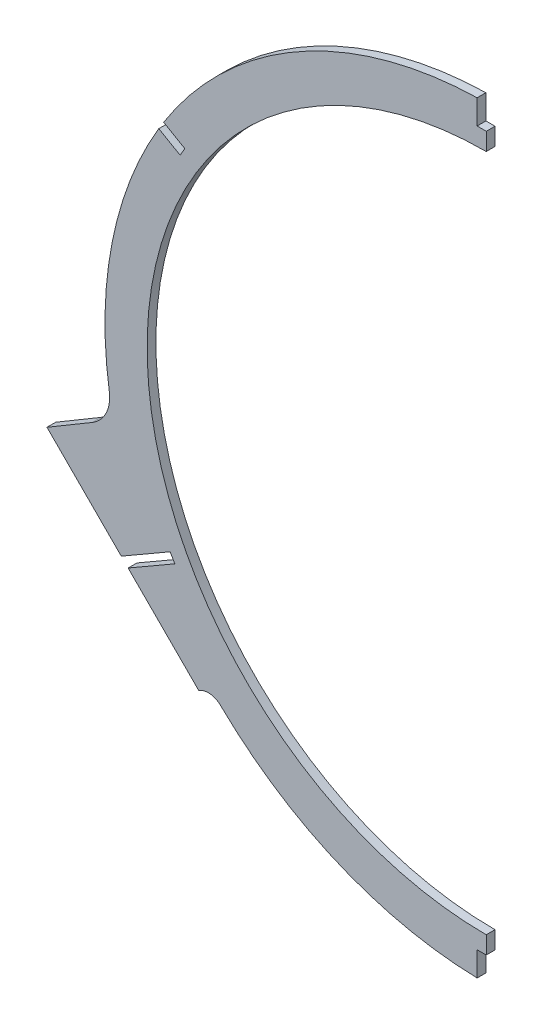
SolidWorks part; units mm, degrees
material "Plywood"
ref_plane "Front Plane" through (0, 0, 0) normal (0, 0, 1) x (1, 0, 0)
ref_plane "Top Plane" through (0, 0, 0) normal (0, 1, 0) x (1, 0, 0)
ref_plane "Right Plane" through (0, 0, 0) normal (1, 0, 0) x (0, 0, -1)
sketch "Sketch1" plane through (0, 0, 0) normal (0, 0, 1) x (1, 0, 0)
  line L0 (0, 0) -> (0, 499.9473) construction
  line L1 (0, -114.7984) -> (0, -129.4545) construction
  line L2 (0, -374.4718) -> (0, 404.2655) construction
  line L3 (-1.651, 142.9921) -> (-1.651, 150.6121) construction
  line L4 (1.651, 142.9921) -> (1.651, 150.6121) construction
  line L5 (-1.651, 142.9921) -> (1.651, 142.9921) construction
  line L6 (136.2041, -53.806) -> (0.0002, 24.7625) construction
  line L7 (-136.2076, -53.7991) -> (0.0002, 24.7625) construction
  line L8 (136.2041, -53.806) -> (0.0002, 24.7625) construction
  line L9 (-136.2076, -53.7991) -> (0.0002, 24.7625) construction
  line L10 (-125.0584, -45.4626) -> (-118.4576, -41.6554) construction
  line L11 (-123.6259, -48.4483) -> (-116.8078, -44.5157) construction
  line L12 (-118.4576, -41.6554) -> (-116.8078, -44.5157) construction
  line L13 (-124.1455, -48.7479) -> (-123.6847, -48.4822) construction
  line L14 (-123.6847, -48.4822) -> (-123.6259, -48.4483) construction
  line L15 (-125.7952, -45.8876) -> (-125.1113, -45.4931) construction
  line L16 (-125.1113, -45.4931) -> (-125.0584, -45.4626) construction
  line L17 (125.4797, -45.7137) -> (125.1075, -45.499) construction
  line L18 (123.8298, -48.5739) -> (123.6807, -48.488) construction
  line L19 (117.0223, -44.647) -> (118.6722, -41.7868) construction
  line L20 (123.6807, -48.488) -> (123.6228, -48.4545) construction
  line L21 (123.6228, -48.4545) -> (117.0223, -44.647) construction
  line L22 (125.1075, -45.499) -> (125.0554, -45.4689) construction
  line L23 (125.0554, -45.4689) -> (118.6722, -41.7868) construction
  line L24 (-107.079, -46.8884) -> (-120.3798, -54.5735)
  line L25 (-108.6638, -44.1348) -> (-121.9647, -51.8199)
  line L28 (-115.4206, -47.9666) -> (-121.9445, -51.7361) construction
  line L29 (-120.2754, -54.5131) -> (-108.646, -44.1245) construction
  line L30 (-114.4607, -49.3188) -> (-122.1124, -53.7399) construction
  line L31 (-113.7686, -50.8257) -> (-120.3665, -54.6379) construction
  line L32 (-115.4206, -47.9666) -> (-113.7686, -50.8257) construction
  line L33 (106.3137, -46.4532) -> (129.9098, -60.0883)
  line L34 (107.9004, -43.7007) -> (131.505, -57.3407)
  line L35 (129.9098, -60.0883) -> (131.505, -57.3407)
  line L36 (129.9098, -60.0883) -> (131.505, -57.3407) construction
  line L37 (107.9004, -43.7007) -> (131.505, -57.3407) construction
  line L38 (106.3137, -46.4532) -> (129.9098, -60.0883) construction
  line L39 (129.9098, -60.0883) -> (107.9004, -43.7007) construction
  line L40 (118.9051, -51.8945) -> (101.8722, -42.0519) construction
  line L41 (120.3631, -54.6438) -> (113.7655, -50.8313)
  line L42 (122.0152, -51.7848) -> (122.0057, -51.7794) construction
  line L43 (113.7655, -50.8313) -> (115.4176, -47.9723)
  line L44 (122.0057, -51.7794) -> (121.9413, -51.7421) construction
  line L45 (121.9413, -51.7421) -> (115.4176, -47.9723)
  line L46 (-108.6638, -44.1348) -> (-121.9647, -51.8199)
  line L47 (-107.079, -46.8884) -> (-120.3798, -54.5735)
  arc A0 (-1.651, 150.6121) -> (-125.0584, -45.4626) centre (0, 12.7) ccw
  circle A1 centre (0, 12.7) radius 120.904
  arc A2 (0, 150.622) -> (-1.651, 150.6121) centre (0, 12.7) ccw
  circle A3 centre (0, 12.7) radius 137.922 construction
  arc A4 (1.651, 150.6121) -> (0, 150.622) centre (0, 12.7) ccw
  arc A5 (-124.3508, -46.9604) -> (-123.6259, -48.4483) centre (0, 12.7) ccw
  arc A6 (-123.6259, -48.4483) -> (-121.9445, -51.7361) centre (0, 12.7) ccw
  arc A7 (-125.0584, -45.4626) -> (-124.3508, -46.9604) centre (0, 12.7) ccw
  arc A8 (124.3477, -46.9667) -> (125.0554, -45.4689) centre (0, 12.7) ccw
  arc A9 (125.0554, -45.4689) -> (1.651, 150.6121) centre (0, 12.7) ccw
  arc A10 (123.6228, -48.4545) -> (124.3477, -46.9667) centre (0, 12.7) ccw
  arc A11 (-121.9153, -51.7914) -> (-121.1641, -53.1919) centre (0, 12.7) ccw
  arc A12 (-120.3665, -54.6379) -> (120.3631, -54.6438) centre (0, 12.7) ccw
  arc A13 (-121.9445, -51.7361) -> (-121.9153, -51.7914) centre (0, 12.7) ccw
  arc A14 (-121.1641, -53.1919) -> (-120.3827, -54.6089) centre (0, 12.7) ccw
  arc A15 (-120.3827, -54.6089) -> (-120.397, -54.5834) centre (0, 12.7) ccw construction
  arc A16 (-120.397, -54.5834) -> (-120.3665, -54.6379) centre (0, 12.7) ccw construction
  arc A17 (120.3936, -54.5893) -> (121.0149, -53.4654) centre (0, 12.7) ccw construction
  arc A18 (121.9413, -51.7421) -> (123.6228, -48.4545) centre (0, 12.7) ccw
  arc A19 (120.3631, -54.6438) -> (120.3936, -54.5893) centre (0, 12.7) ccw construction
  arc A20 (121.0149, -53.4654) -> (121.9121, -51.7974) centre (0, 12.7) ccw construction
  arc A21 (121.9121, -51.7974) -> (121.9413, -51.7421) centre (0, 12.7) ccw construction
  spline S0 degree 3 poles (106.3137, -46.4532) (106.8426, -45.5357) (107.3715, -44.6182) (107.9004, -43.7007) knots 0 0 0 0 1 1 1 1 weights 1 1 1 1
  spline S1 degree 3 poles (-66.0123, 133.6164) (-70.0128, 131.4329) (-73.8716, 129.0699) (-81.3156, 123.9975) (-84.9009, 121.288) (-91.7995, 115.5249) (-95.113, 112.4712) (-99.0811, 108.4341) (-99.866, 107.6157) (-101.4182, 105.9565) (-102.1865, 105.1147) (-104.4569, 102.5643) (-105.9223, 100.8334) (-110.1768, 95.5512) (-115.4725, 88.2691) (-120.0285, 80.5179) (-123.1654, 74.5269) (-124.1643, 72.5002) (-125.5914, 69.415) (-126.0551, 68.3791) (-126.9587, 66.292) (-127.3989, 65.2397) (-129.5278, 59.9684) (-131.0098, 55.7) (-133.5456, 47.0638) (-134.5993, 42.696) (-136.2795, 33.8613) (-136.906, 29.3944) (-137.415, 23.7472) (-137.5031, 22.6146) (-137.6514, 20.3429) (-137.7116, 19.2049) (-137.8496, 15.7999) (-137.8852, 13.5361) (-137.8263, 6.7629) (-137.3062, -2.2197) (-135.9163, -11.1068) (-134.5433, -17.7359) (-134.0304, -19.9395) (-132.8922, -24.3345) (-132.2653, -26.5303) (-130.2347, -33.03) (-128.6774, -37.2656) (-126.1245, -43.2881) (-125.286, -45.1501) (-124.4066, -46.9926) knots 0 0 0 0 0.03125 0.03125 0.0625 0.0625 0.09375 0.09375 0.101563 0.101563 0.109375 0.109375 0.125 0.125 0.15625 0.1875 0.1875 0.203125 0.203125 0.210938 0.210938 0.21875 0.21875 0.25 0.25 0.28125 0.28125 0.3125 0.3125 0.320313 0.320313 0.328125 0.328125 0.34375 0.34375 0.375 0.40625 0.40625 0.421875 0.421875 0.4375 0.4375 0.46875 0.46875 0.48295 0.48295 0.48295 0.48295 construction
  spline S2 degree 3 poles (-2953.7904, 2461.9899) (-820.777, 189.8449) (-138.9507, -249.535) (81.4542, -98.9353) (85.033, -96.2237) (91.9188, -90.4573) (95.2258, -87.4025) (99.1858, -83.3647) (99.9691, -82.5461) (101.5182, -80.8868) (102.2849, -80.0449) (104.5506, -77.4941) (106.013, -75.7632) (110.2586, -70.4809) (112.9006, -66.8403) (117.8152, -59.3254) (120.0877, -55.4512) (123.2166, -49.4629) (124.2129, -47.4373) (125.6361, -44.3538) (126.0986, -43.3185) (126.9997, -41.2327) (127.4386, -40.181) (129.5618, -34.9121) (131.0396, -30.646) (133.5674, -22.0152) (134.6173, -17.6505) (136.2906, -8.8227) (136.914, -4.3596) (137.4197, 1.2823) (137.5071, 2.4139) (137.6542, 4.6834) (137.7138, 5.8206) (137.85, 9.2232) (137.8846, 11.4853) (137.8228, 18.2533) (137.2995, 27.2283) (135.9081, 36.1069) (134.5347, 42.7292) (134.0218, 44.9305) (132.8839, 49.3207) (132.2571, 51.5145) (130.2267, 58.0093) (128.67, 62.2416) (125.1615, 70.5162) (123.2097, 74.5586) (118.9108, 82.4534) (116.5637, 86.3058) (113.3753, 90.999) (112.7241, 91.9325) (111.3996, 93.7822) (110.7272, 94.697) (108.6802, 97.4113) (107.2757, 99.181) (102.9447, 104.3725) (96.8571, 110.9816) (90.1513, 116.9722) (84.8861, 121.2292) (83.0917, 122.6088) (80.3399, 124.6181) (79.4113, 125.2786) (77.543, 126.5731) (76.6028, 127.2075) (71.8708, 130.3161) (67.9881, 132.6004) (60.0328, 136.7739) (55.9603, 138.6631) (47.6249, 142.0446) (43.3619, 143.537) (37.9102, 145.1462) (36.8136, 145.4551) (34.6205, 146.0438) (33.5224, 146.3241) (30.2234, 147.1229) (28.0179, 147.5997) (21.3832, 148.8649) (16.9358, 149.4889) (7.993, 150.3014) (3.4975, 150.4899) (-3.2824, 150.4396) (-5.5486, 150.3672) (-10.0934, 150.1088) (-12.3559, 149.9236) (-19.101, 149.2046) (-23.5473, 148.5072) (-32.3412, 146.6856) (-36.6887, 145.5614) (-43.1354, 143.5526) (-45.2718, 142.8291) (-49.5193, 141.273) (-51.6323, 140.4395) (-369.2659, 5.9249) (-132.0865, -1278.1783) (677.8124, -3754.3927) knots -1.791229 -1.791229 -1.791229 -1.791229 0.03125 0.03125 0.0625 0.0625 0.09375 0.09375 0.101563 0.101563 0.109375 0.109375 0.125 0.125 0.15625 0.15625 0.1875 0.1875 0.203125 0.203125 0.210938 0.210938 0.21875 0.21875 0.25 0.25 0.28125 0.28125 0.3125 0.3125 0.320313 0.320313 0.328125 0.328125 0.34375 0.34375 0.375 0.40625 0.40625 0.421875 0.421875 0.4375 0.4375 0.46875 0.46875 0.5 0.5 0.53125 0.53125 0.539062 0.539062 0.546875 0.546875 0.5625 0.5625 0.59375 0.625 0.625 0.640625 0.640625 0.648437 0.648437 0.65625 0.65625 0.6875 0.6875 0.71875 0.71875 0.75 0.75 0.757812 0.757812 0.765625 0.765625 0.78125 0.78125 0.8125 0.8125 0.84375 0.84375 0.859375 0.859375 0.875 0.875 0.90625 0.90625 0.9375 0.9375 0.953125 0.953125 0.96875 0.96875 3.320852 3.320852 3.320852 3.320852 only from (66.1767, -108.566) to (-66.0123, 133.6164)
  spline S3 degree 3 poles (66.1767, -108.566) (70.1708, -106.3789) (74.0231, -104.0129) (81.4542, -98.9353) (85.033, -96.2237) (91.9188, -90.4573) (95.2258, -87.4025) (99.1858, -83.3647) (99.9691, -82.5461) (101.5182, -80.8868) (102.2849, -80.0449) (104.5506, -77.4941) (106.013, -75.7632) (110.2586, -70.4809) (112.9006, -66.8403) (117.8152, -59.3254) (120.0877, -55.4512) (123.2166, -49.4629) (124.2129, -47.4373) (125.6361, -44.3538) (126.0986, -43.3185) (126.9997, -41.2327) (127.4386, -40.181) (129.5618, -34.9121) (131.0396, -30.646) (133.5674, -22.0152) (134.6173, -17.6505) (136.2906, -8.8227) (136.914, -4.3596) (137.4197, 1.2823) (137.5071, 2.4139) (137.6542, 4.6834) (137.7138, 5.8206) (137.85, 9.2232) (137.8846, 11.4853) (137.8228, 18.2533) (137.2995, 27.2283) (135.9081, 36.1069) (134.5347, 42.7292) (134.0218, 44.9305) (132.8839, 49.3207) (132.2571, 51.5145) (130.2267, 58.0093) (128.67, 62.2416) (125.1615, 70.5162) (123.2097, 74.5586) (118.9108, 82.4534) (116.5637, 86.3058) (113.3753, 90.999) (112.7241, 91.9325) (111.3996, 93.7822) (110.7272, 94.697) (108.6802, 97.4113) (107.2757, 99.181) (102.9447, 104.3725) (96.8571, 110.9816) (90.1513, 116.9722) (84.8861, 121.2292) (83.0917, 122.6088) (80.3399, 124.6181) (79.4113, 125.2786) (77.543, 126.5731) (76.6028, 127.2075) (71.8708, 130.3161) (67.9881, 132.6004) (60.0328, 136.7739) (55.9603, 138.6631) (47.6249, 142.0446) (43.3619, 143.537) (37.9102, 145.1462) (36.8136, 145.4551) (34.6205, 146.0438) (33.5224, 146.3241) (30.2234, 147.1229) (28.0179, 147.5997) (21.3832, 148.8649) (16.9358, 149.4889) (7.993, 150.3014) (3.4975, 150.4899) (-3.2824, 150.4396) (-5.5486, 150.3672) (-10.0934, 150.1088) (-12.3559, 149.9236) (-19.101, 149.2046) (-23.5473, 148.5072) (-32.3412, 146.6856) (-36.6887, 145.5614) (-43.1354, 143.5526) (-45.2718, 142.8291) (-49.5193, 141.273) (-51.6323, 140.4395) (-57.9206, 137.7764) (-62.0153, 135.798) (-66.0123, 133.6164) knots 0 0 0 0 0.03125 0.03125 0.0625 0.0625 0.09375 0.09375 0.101563 0.101563 0.109375 0.109375 0.125 0.125 0.15625 0.15625 0.1875 0.1875 0.203125 0.203125 0.210938 0.210938 0.21875 0.21875 0.25 0.25 0.28125 0.28125 0.3125 0.3125 0.320313 0.320313 0.328125 0.328125 0.34375 0.34375 0.375 0.40625 0.40625 0.421875 0.421875 0.4375 0.4375 0.46875 0.46875 0.5 0.5 0.53125 0.53125 0.539062 0.539062 0.546875 0.546875 0.5625 0.5625 0.59375 0.625 0.625 0.640625 0.640625 0.648437 0.648437 0.65625 0.65625 0.6875 0.6875 0.71875 0.71875 0.75 0.75 0.757812 0.757812 0.765625 0.765625 0.78125 0.78125 0.8125 0.8125 0.84375 0.84375 0.859375 0.859375 0.875 0.875 0.90625 0.90625 0.9375 0.9375 0.953125 0.953125 0.96875 0.96875 1 1 1 1 construction
  spline S4 degree 3 poles (-124.4066, -46.9926) (-124.169, -47.4906) (-123.9283, -47.9871) (-123.6847, -48.4822) knots 0.48295 0.48295 0.48295 0.48295 0.486788 0.486788 0.486788 0.486788 construction
  spline S5 degree 3 poles (-123.6847, -48.4822) (-122.846, -50.1865) (-121.9718, -51.874) (-118.9108, -57.4955) (-116.5612, -61.3517) (-113.369, -66.0497) (-112.7169, -66.9844) (-111.3913, -68.8351) (-110.7184, -69.7503) (-108.6697, -72.4662) (-107.264, -74.2369) (-102.929, -79.4315) (-96.8353, -86.0447) (-90.1214, -92.0392) (-84.8493, -96.299) (-83.0524, -97.6795) (-80.2967, -99.6899) (-79.367, -100.3507) (-77.4971, -101.6451) (-76.5559, -102.2795) (-71.8198, -105.3881) (-67.9332, -107.6723) (-59.9695, -111.8452) (-55.8924, -113.7339) (-47.5468, -117.114) (-43.2782, -118.6053) (-37.8188, -120.2127) (-36.7216, -120.521) (-34.5268, -121.1085) (-33.4279, -121.3881) (-30.1264, -122.185) (-27.9191, -122.6605) (-21.2788, -123.9216) (-16.8274, -124.5426) (-7.8757, -125.3484) (-3.3755, -125.5332) (3.4122, -125.4766) (5.6812, -125.4019) (10.231, -125.1387) (12.493, -124.9512) (19.2413, -124.2249) (23.6899, -123.5224) (32.4889, -121.6898) (36.8393, -120.5597) (43.2904, -118.5412) (45.4283, -117.8143) (48.6163, -116.6419) (49.6759, -116.2374) (51.7885, -115.4006) (52.8426, -114.968) (58.0839, -112.7404) (62.1792, -110.755) (66.1767, -108.566) knots 0.486788 0.486788 0.486788 0.486788 0.5 0.5 0.53125 0.53125 0.539062 0.539062 0.546875 0.546875 0.5625 0.5625 0.59375 0.625 0.625 0.640625 0.640625 0.648437 0.648437 0.65625 0.65625 0.6875 0.6875 0.71875 0.71875 0.75 0.75 0.757812 0.757812 0.765625 0.765625 0.78125 0.78125 0.8125 0.8125 0.84375 0.84375 0.859375 0.859375 0.875 0.875 0.90625 0.90625 0.9375 0.9375 0.953125 0.953125 0.960937 0.960937 0.96875 0.96875 1 1 1 1 construction
  spline S6 degree 3 poles (-108.6638, -44.1348) (-108.1355, -45.0527) (-107.6073, -45.9705) (-107.079, -46.8884) knots 0 0 0 0 1 1 1 1 weights 1 1 1 1
  spline S7 degree 3 poles (-121.9647, -51.8199) (-121.4364, -52.7377) (-120.9081, -53.6556) (-120.3798, -54.5735) knots 0 0 0 0 1 1 1 1 weights 1 1 1 1
  spline S8 degree 3 poles (-1893.2904, -3504.9521) (-555.0999, -1197.2897) (777.7409, 1114.8667) (2098.5249, 3419.8483) knots -1257.71527 -1257.71527 -1257.71527 -1257.71527 1261.282288 1261.282288 1261.282288 1261.282288 weights 1.001261 0.999578 0.999579 1.001266 only from (106.3137, -46.4532) to (107.9004, -43.7007)
  spline S9 degree 3 poles (-121.8597, -51.7592) (-121.5948, -52.2177) (-121.3299, -52.6762) (-121.065, -53.1347) knots 0 0 0 0 0.5 0.5 0.5 0.5 weights 1 1 1 1 construction
  spline S12 degree 3 poles (-2107.5184, 3411.1282) (-794.411, 1112.1626) (537.2029, -1201.4874) (1876.5356, -3511.0638) knots -1261.624621 -1261.624621 -1261.624621 -1261.624621 1257.384167 1257.384167 1257.384167 1257.384167 weights 1.00204 0.999326 0.99932 1.002023 only from (-121.9647, -51.8199) to (-120.3798, -54.5735)
  spline S13 degree 3 poles (-2094.7969, 3419.3607) (-780.7303, 1119.4679) (550.7427, -1194.0569) (1889.8709, -3504.2883) knots -1261.518414 -1261.518414 -1261.518414 -1261.518414 1257.484402 1257.484402 1257.484402 1257.484402 weights 1.00184 0.999392 0.999387 1.001825 only from (-108.6638, -44.1348) to (-107.079, -46.8884)
  point P7 (0, -125.5003)
  point P8 (0, 150.4602)
  point P25 (-125.0584, -45.4626)
  point P38 (123.6228, -48.4545)
  dimension "D2" = 275.844
  dimension "D1" = 275.9605
  dimension "D3" = 12.7
  dimension "D5" = 3.302
  dimension "D6" = 7.62
  dimension "D7" = 3.302
  dimension "D8" = 7.62
  dimension "D9" = 3.302
  dimension "D10" = 7.62
  dimension "D11" = 3.302
  dimension "D12" = 7.62
  dimension "D13" = 3.302
  dimension "D14" = 7.62
  dimension "D4" = 17.018
sketch "Sketch2" plane through (248.2736, -245.0135, 0) normal (0, 0, -1) x (0, -1, 0)
  line L3 (-245.0135, 248.2736) -> (-427.6569, 248.2736) construction
  circle A1 centre (-257.7135, 248.2736) radius 137.922
  circle A16 centre (-257.7135, 248.2736) radius 122.682
  dimension "D1" = 12.7
  dimension "D2" = 275.844
  dimension "D3" = 15.24
extrude "Boss-Extrude2" add sketch "Sketch2" along normal mid plane 3.175
sketch "Sketch3" plane through (0, 0, 0) normal (1, 0, 0) x (0, 0, -1)
  line L1 (-141.282, 263.3615) -> (149.6958, 263.3615)
  line L2 (-141.282, 263.3615) -> (-141.282, -241.4673)
  line L3 (-141.282, -241.4673) -> (149.6958, -241.4673)
  line L4 (149.6958, 263.3615) -> (149.6958, -241.4673)
extrude "Cut-Extrude1" cut sketch "Sketch3" along normal through all
sketch "Sketch4" plane through (0, 0, 0) normal (0, 0, 1) x (1, 0, 0)
  line L0 (0, 0) -> (-214.0513, 0) construction
  line L1 (-158.912, -30.4526) -> (-104.0071, -85.469)
  line L2 (-134.8591, -16.205) -> (-158.912, -30.4526)
  arc A0 (-104.0071, -85.469) -> (-167.1792, -137.0342) centre (409.8935, -779.5232) ccw construction
  arc A1 (0, 150.622) -> (0, -125.222) centre (0, 12.7) ccw construction
  arc A2 (-99.8692, -82.4242) -> (-104.0071, -85.469) centre (409.8935, -779.5232) ccw
  arc A3 (-134.8591, -16.205) -> (-99.8692, -82.4242) centre (0, 12.7) ccw
  point P6 (-99.8692, -82.4242)
  dimension "D3" = 54.61
  dimension "D5" = 863.6
  dimension "D1" = 99.8692
  dimension "D2" = 82.4242
  dimension "D4" = 67.31
  dimension "D6" = 45.058
  dimension "D7" = 133.9931
  dimension "D8" = 134.8591
  dimension "D9" = 30.64
extrude "Boss-Extrude3" add sketch "Sketch4" along normal mid plane 3.175
fillet "Fillet2" radius 6.35 1 edges at (-99.8692, -82.4242, 0)
fillet "Fillet3" radius 12.7 1 edges at (-134.8591, -16.205, 0)
sketch "Sketch5" plane through (0, 0, -1.5875) normal (0, 0, -1) x (-1, 0, 0)
  line L0 (0, 0) -> (0, 135.382) construction
  line L1 (0, 135.382) -> (0, 141.732) construction
  line L2 (0, 150.622) -> (0, 135.382) construction
  line L4 (0, 141.732) -> (3.302, 141.732)
  line L5 (0, 141.732) -> (0, 151.892)
  line L6 (0, 151.892) -> (3.302, 151.892)
  line L7 (3.302, 141.732) -> (3.302, 151.892)
  line L14 (103.544, 78.6136) -> (105.2331, 75.688) construction
  line L15 (104.3885, 77.1508) -> (0, 16.882) construction
  line L16 (103.544, 78.6136) -> (105.2331, 75.688) construction
  line L17 (103.544, 78.6136) -> (109.0433, 81.7886) construction
  line L18 (105.2331, 75.688) -> (110.7324, 78.863) construction
  line L19 (109.0433, 81.7886) -> (110.7324, 78.863) construction
  line L20 (109.0433, 81.7886) -> (110.7324, 78.863)
  line L21 (109.0433, 81.7886) -> (118.3449, 87.1589)
  line L22 (110.7324, 78.863) -> (120.034, 84.2333)
  line L23 (118.3449, 87.1589) -> (120.034, 84.2333)
  line L24 (0, 16.882) -> (0, -109.982) construction
  line L25 (0, -109.982) -> (0, -116.332) construction
  line L26 (0, -109.982) -> (0, -125.222) construction
  line L28 (0, -116.332) -> (3.302, -116.332)
  line L29 (0, -116.332) -> (0, -126.6527)
  line L30 (0, -126.6527) -> (3.302, -126.6527)
  line L31 (3.302, -116.332) -> (3.302, -126.6527)
  line L37 (107.1657, -46.9405) -> (108.8548, -44.0149) construction
  line L38 (108.0103, -45.4777) -> (0, 16.882) construction
  line L39 (107.1657, -46.9405) -> (108.8548, -44.0149) construction
  line L40 (107.1657, -46.9405) -> (112.665, -50.1155) construction
  line L41 (108.8548, -44.0149) -> (114.3541, -47.1899) construction
  line L42 (112.665, -50.1155) -> (114.3541, -47.1899) construction
  line L43 (112.665, -50.1155) -> (114.3541, -47.1899)
  line L44 (112.665, -50.1155) -> (134.6621, -62.8155)
  line L45 (114.3541, -47.1899) -> (136.3512, -59.8899)
  line L46 (134.6621, -62.8155) -> (136.3512, -59.8899)
  ellipse E3 centre (0, 6.1144) end of major axis (133.35, 6.1144) minor radius 132.8077 (3.302, -126.6527) -> (98.3628, -83.5583) ccw construction
  point P13 (104.3885, 77.1508)
  point P26 (108.0103, -45.4777)
  dimension "D1" = 135.382
  dimension "D2" = 6.35
  dimension "D3" = 10.16
  dimension "D4" = 3.302
  dimension "D5" = 16.882
  dimension "D6" = 120
  dimension "D7" = 120.5375
  dimension "D8" = 3.3782
  dimension "D9" = 6.35
  dimension "D10" = 126.864
  dimension "D11" = 6.35
  dimension "D12" = 10.3207
  dimension "D13" = 3.302
  dimension "D14" = 60
  dimension "D15" = 124.7195
  dimension "D16" = 3.3782
  dimension "D17" = 6.35
  dimension "D18" = 25.4
extrude "Cut-Extrude2" cut sketch "Sketch5" against normal through all
equation "\"slotwidth\"=0.13"
equation "\"D11@Sketch1\"=\"slotwidth\""
